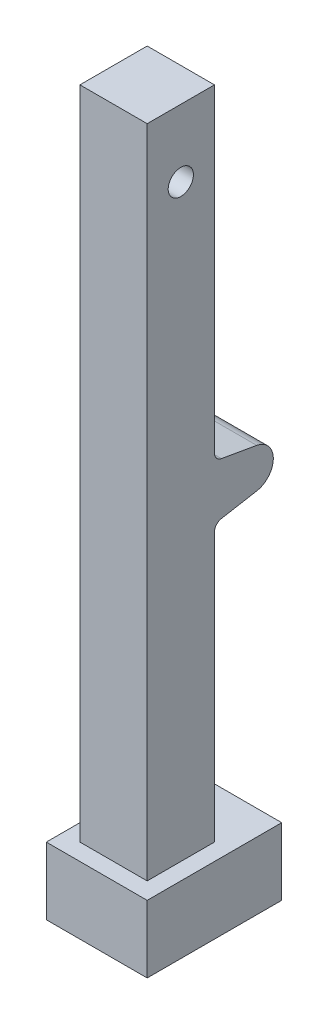
SolidWorks part; units mm, degrees
ref_plane "Front Plane" through (0, 0, 0) normal (1, 0, 0) x (0, 1, 0)
ref_plane "Top Plane" through (0, 0, 0) normal (0, 0, 1) x (0, 1, 0)
ref_plane "Right Plane" through (0, 0, 0) normal (0, 1, 0) x (-1, 0, 0)
sketch "Sketch1" plane through (0, 0, 0) normal (1, 0, 0) x (0, 1, 0)
  line L0 (-900, -100) -> (-2000, -100)
  line L1 (200, 100) -> (-2000, 100)
  line L2 (200, 100) -> (200, -100)
  line L3 (200, -100) -> (-800, -100)
  line L4 (-2000, 100) -> (-2000, -100)
  line L5 (-1950, 150) -> (-1750, 150)
  line L6 (-1950, 150) -> (-1950, -250)
  line L7 (-1950, -250) -> (-1750, -250)
  line L8 (-1750, 150) -> (-1750, -250)
  line L10 (-800, -100) -> (-800, -275)
  line L11 (-800, -275) -> (-900, -275)
  line L12 (-900, -100) -> (-900, -275)
  circle A0 centre (0, 0) radius 37.5
  point P4 (200, 0)
  point P16 (-850, -275)
  dimension "D4" = 75
  dimension "D9" = 850
  dimension "D1" = 200
  dimension "D2" = 2000
  dimension "D3" = 200
  dimension "D5" = 50
  dimension "D6" = 200
  dimension "D7" = 50
  dimension "D8" = 400
  dimension "D10" = 100
  dimension "D11" = 175
extrude "Boss-Extrude1" add sketch "Sketch1" along normal mid plane 200 contours L1 L8 L3 L2 A0 | L8 L1 L6 L3 | L6 L1 L4 L3 region at (0, -786.7503, -8.1404) region at (0, -1850, 0) region at (0, -1975, 0)
draft "Draft1" type of draft neutral plane draft angle 10 faces to draft 2 face at (0, -800, -187.5) face at (0, -900, -187.5) neutral plane through (100, 0, -275) neutral plane normal (0, 0, -1) parameters "D1"=10
extrude "Boss-Extrude2" add sketch "Sketch1<3>" along normal mid plane 300 contours L5 L8 L7 L6
sketch "Sketch1<3>" plane through (0, 0, 0) normal (1, 0, 0) x (0, 1, 0) same geometry as "Sketch1"
fillet "Fillet1" 2 edges at (0, -900, -275) (0, -800, -275) type full round first side face at (0, -915.4286, -187.5) second side face at (0, -784.5714, -187.5) middle face at (0, -850, -275)
fillet "Fillet2" radius 25 2 edges at (0, -769.1428, -100) (0, -930.8572, -100)
